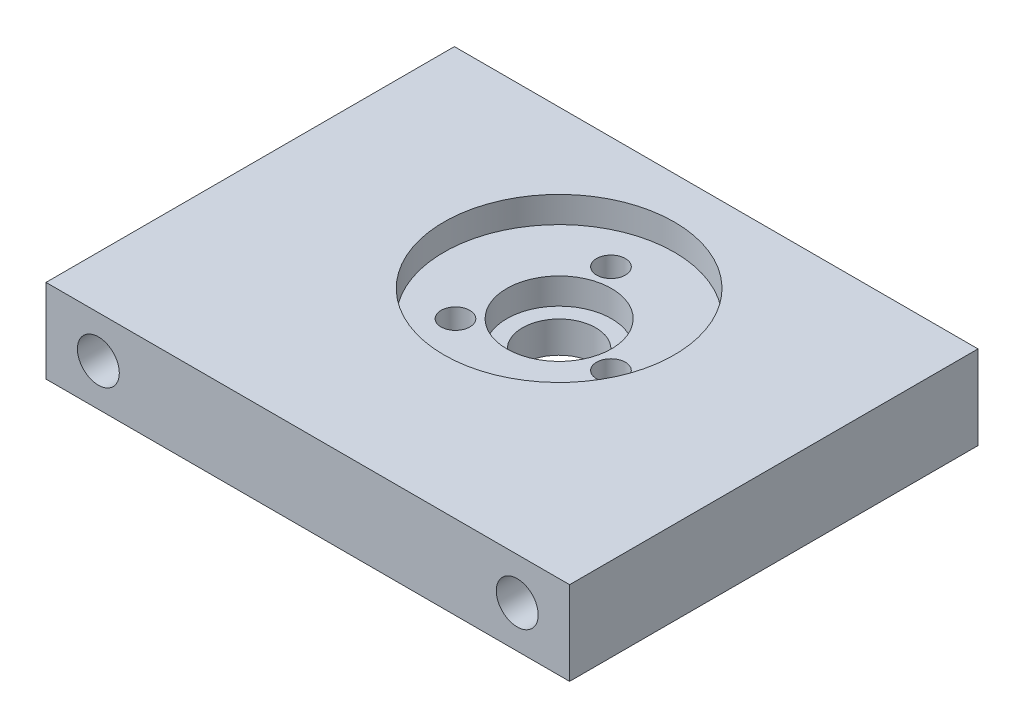
SolidWorks part; units mm, degrees
material "PVC rigide"
ref_plane "Plan de face" through (0, 0, 0) normal (0, 0, 1) x (1, 0, 0)
ref_plane "Plan de dessus" through (0, 0, 0) normal (0, 1, 0) x (1, 0, 0)
ref_plane "Plan de droite" through (0, 0, 0) normal (1, 0, 0) x (0, 0, -1)
sketch "Esquisse1" plane through (0, 0, 0) normal (0, 1, 0) x (1, 0, 0)
  line L1 (-25, 19.5) -> (25, 19.5)
  line L2 (-25, 19.5) -> (-25, -19.5)
  line L3 (-25, -19.5) -> (25, -19.5)
  line L4 (25, 19.5) -> (25, -19.5)
  line L5 (-25, -19.5) -> (25, 19.5) construction
  line L6 (25, -19.5) -> (-25, 19.5) construction
  point P4 (0, 0)
  dimension "D1" = 50
  dimension "D2" = 39
extrude "Boss.-Extru.1" add sketch "Esquisse1" along normal blind 8
sketch "Esquisse2" plane through (0, 8, 0) normal (0, 1, 0) x (1, 0, 0)
  line L1 (-25, 19.5) -> (25, 19.5) construction
  line L2 (0, 19.5) -> (0, -19.5) construction
  line L3 (25, 19.5) -> (-25, 19.5) construction
  line L4 (-25, -19.5) -> (25, -19.5) construction
  circle A0 centre (0, 4.5) radius 5
  dimension "D2" = 10
  dimension "D1" = 15
extrude "Enlèv. mat.-Extru.1" cut sketch "Esquisse2" against normal blind 5
sketch "Esquisse3" plane through (0, 8, 0) normal (0, 1, 0) x (1, 0, 0)
  line L0 (-4.9497, -0.4497) -> (-1.8117, 11.2615) construction
  line L1 (-1.8117, 11.2615) -> (6.7615, 2.6883) construction
  line L2 (6.7615, 2.6883) -> (-4.9497, -0.4497) construction
  line L3 (0, 4.5) -> (-1.8117, 11.2615) construction
  line L5 (0, -19.5) -> (0, 19.5) construction
  line L6 (-25, -19.5) -> (25, -19.5) construction
  line L7 (25, 19.5) -> (-25, 19.5) construction
  circle A0 centre (0, 4.5) radius 7 construction
  circle A1 centre (-1.8117, 11.2615) radius 1.375
  circle A2 centre (6.7615, 2.6883) radius 1.375
  circle A3 centre (-4.9497, -0.4497) radius 1.375
  circle A4 centre (0, 4.5) radius 3.5
  dimension "D1" = 14
  dimension "D2" = 2.75
  dimension "D3" = 7
  dimension "D4" = 15
extrude "Enlèv. mat.-Extru.2" cut sketch "Esquisse3" against normal blind 15
sketch "Esquisse4" plane through (0, 8, 0) normal (0, 1, 0) x (1, 0, 0)
  circle A0 centre (0, 4.5) radius 11
  dimension "D1" = 22
extrude "Enlèv. mat.-Extru.3" cut sketch "Esquisse4" against normal blind 2.5
sketch "Esquisse5" plane through (0, 0, 0) normal (0, -1, 0) x (1, 0, 0)
  circle A0 centre (-4.9497, 0.4497) radius 2.25
  circle A1 centre (6.7615, -2.6883) radius 2.25
  circle A2 centre (-1.8117, -11.2615) radius 2.25
  dimension "D1" = 4.5
extrude "Enlèv. mat.-Extru.4" cut sketch "Esquisse5" against normal blind 2.5
sketch "Esquisse6" plane through (0, 0, 19.5) normal (0, 0, 1) x (1, 0, 0)
  line L0 (-25, 4) -> (25, 4) construction
  line L1 (-25, 8) -> (-25, 0) construction
  line L2 (25, 8) -> (25, 0) construction
  circle A0 centre (-20, 4) radius 2
  circle A1 centre (20, 4) radius 2
  dimension "D1" = 4
  dimension "D2" = 5
  dimension "D3" = 5
extrude "Enlèv. mat.-Extru.5" cut sketch "Esquisse6" against normal blind 10
